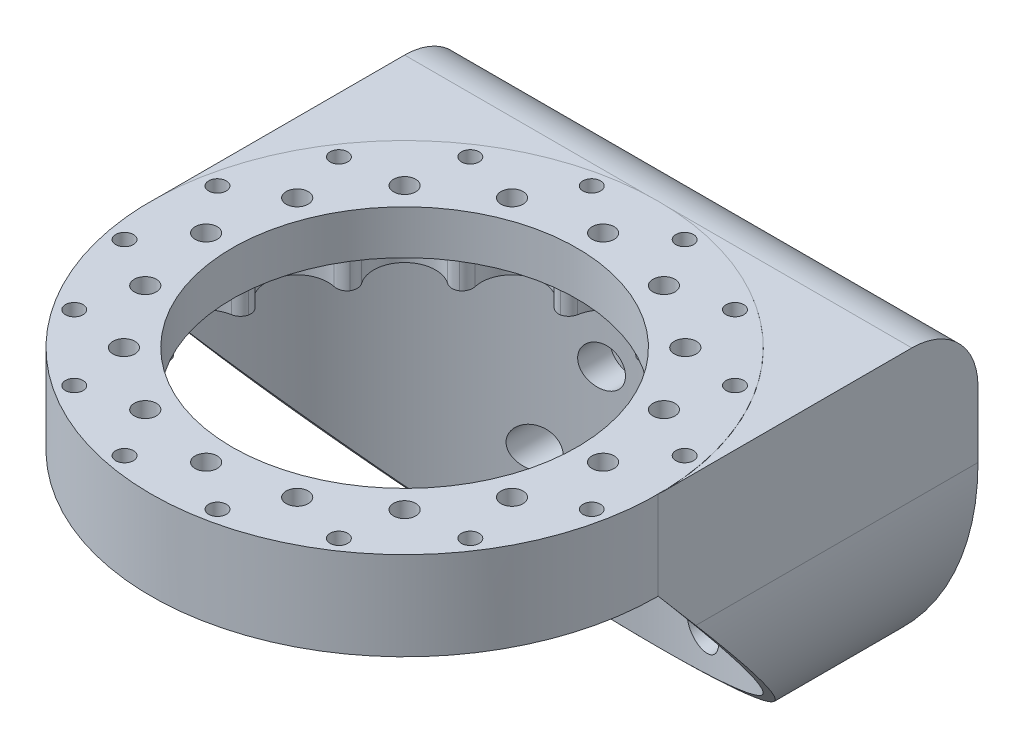
SolidWorks part; units mm, degrees
ref_plane "Front Plane" through (0, 0, 0) normal (0, 0, 1) x (1, 0, 0)
ref_plane "Top Plane" through (0, 0, 0) normal (0, 1, 0) x (1, 0, 0)
ref_plane "Right Plane" through (0, 0, 0) normal (1, 0, 0) x (0, 0, -1)
sketch "Sketch1" plane through (0, 0, 0) normal (0, 1, 0) x (1, 0, 0)
  line L0 (-10.5349, 52.9624) -> (0, 0) construction
  line L1 (0, 0) -> (24.6214, 0) construction
  circle A12 centre (0, 0) radius 39.1
  circle A13 centre (0, 0) radius 57.5
  circle A14 centre (0, 0) radius 54 construction
  circle A15 centre (-10.5349, 52.9624) radius 2
  circle A16 centre (10.5349, 52.9624) radius 2
  circle A17 centre (30.0008, 44.8994) radius 2
  circle A18 centre (44.8994, 30.0008) radius 2
  circle A19 centre (52.9624, 10.5349) radius 2
  circle A20 centre (52.9624, -10.5349) radius 2
  circle A21 centre (44.8994, -30.0008) radius 2
  circle A22 centre (30.0008, -44.8994) radius 2
  circle A23 centre (10.5349, -52.9624) radius 2
  circle A24 centre (-10.5349, -52.9624) radius 2
  circle A25 centre (-30.0008, -44.8994) radius 2
  circle A26 centre (-44.8994, -30.0008) radius 2
  circle A47 centre (-52.9624, -10.5349) radius 2
  circle A48 centre (-52.9624, 10.5349) radius 2
  circle A49 centre (-44.8994, 30.0008) radius 2
  circle A50 centre (-30.0008, 44.8994) radius 2
  point P21 (0, 0)
  point P28 (0, 0)
  point P56 (0, 0)
  point P60 (0, 0)
  dimension "D1" = 101.25
  dimension "D4" = 115
  dimension "D5" = 78.2
  dimension "D6" = 108
  dimension "D7" = 4
  dimension "D8" = 16
extrude "Boss-Extrude1" add sketch "Sketch1" along normal blind 10
sketch "Sketch2" plane through (0, 10, 0) normal (0, 1, 0) x (1, 0, 0)
  circle A0 centre (0, 0) radius 45 construction
  circle A1 centre (0, 45) radius 2.5
  circle A2 centre (17.2208, 41.5746) radius 2.5
  circle A3 centre (31.8198, 31.8198) radius 2.5
  circle A4 centre (41.5746, 17.2208) radius 2.5
  circle A5 centre (45, 0) radius 2.5
  circle A6 centre (41.5746, -17.2208) radius 2.5
  circle A7 centre (31.8198, -31.8198) radius 2.5
  circle A8 centre (17.2208, -41.5746) radius 2.5
  circle A9 centre (0, -45) radius 2.5
  circle A10 centre (-17.2208, -41.5746) radius 2.5
  circle A11 centre (-31.8198, -31.8198) radius 2.5
  circle A12 centre (-41.5746, -17.2208) radius 2.5
  circle A13 centre (-45, 0) radius 2.5
  circle A14 centre (-41.5746, 17.2208) radius 2.5
  circle A15 centre (-31.8198, 31.8198) radius 2.5
  circle A16 centre (-17.2208, 41.5746) radius 2.5
  point P27 (0, 0)
  dimension "D1" = 90
  dimension "D2" = 5
  dimension "D3" = 16
extrude "Cut-Extrude1" cut sketch "Sketch2" against normal blind 10
sketch "Sketch4" plane through (0, 0, 0) normal (0, 1, 0) x (1, 0, 0)
  circle A0 centre (0, 0) radius 45 construction
  circle A1 centre (0, 45) radius 5
  circle A2 centre (0, 45) radius 2.5
  circle A3 centre (17.2208, 41.5746) radius 2.5
  circle A4 centre (31.8198, 31.8198) radius 2.5
  circle A5 centre (41.5746, 17.2208) radius 2.5
  circle A6 centre (45, 0) radius 2.5
  circle A7 centre (41.5746, -17.2208) radius 2.5
  circle A8 centre (31.8198, -31.8198) radius 2.5
  circle A9 centre (17.2208, -41.5746) radius 2.5
  circle A10 centre (0, -45) radius 2.5
  circle A11 centre (-17.2208, -41.5746) radius 2.5
  circle A12 centre (-31.8198, -31.8198) radius 2.5
  circle A13 centre (17.2208, 41.5746) radius 5
  circle A14 centre (31.8198, 31.8198) radius 5
  circle A15 centre (41.5746, 17.2208) radius 5
  circle A16 centre (45, 0) radius 5
  circle A17 centre (41.5746, -17.2208) radius 5
  circle A18 centre (31.8198, -31.8198) radius 5
  circle A19 centre (17.2208, -41.5746) radius 5
  circle A20 centre (0, -45) radius 5
  circle A21 centre (-17.2208, -41.5746) radius 5
  circle A22 centre (-31.8198, -31.8198) radius 5
  circle A23 centre (-41.5746, -17.2208) radius 5
  circle A24 centre (-45, 0) radius 5
  circle A25 centre (-41.5746, 17.2208) radius 5
  circle A26 centre (-31.8198, 31.8198) radius 5
  circle A27 centre (-17.2208, 41.5746) radius 5
  circle A28 centre (-41.5746, -17.2208) radius 2.5
  circle A29 centre (-45, 0) radius 2.5
  circle A30 centre (-41.5746, 17.2208) radius 2.5
  circle A31 centre (-31.8198, 31.8198) radius 2.5
  circle A32 centre (-17.2208, 41.5746) radius 2.5
  point P29 (0, 0)
  point P50 (0, 0)
  dimension "D1" = 10
  dimension "D2" = 16
  dimension "D3" = 16
extrude "Boss-Extrude3" add sketch "Sketch4" against normal blind 0.4
sketch "Sketch5" plane through (0, 0, 0) normal (0, -1, 0) x (1, 0, 0)
  circle A0 centre (0, 0) radius 57.5
  circle A1 centre (0, 0) radius 45
  circle A2 centre (0, 45) radius 7
  circle A3 centre (17.2208, 41.5746) radius 7
  circle A4 centre (31.8198, 31.8198) radius 7
  circle A5 centre (41.5746, 17.2208) radius 7
  circle A6 centre (45, 0) radius 7
  circle A7 centre (41.5746, -17.2208) radius 7
  circle A8 centre (31.8198, -31.8198) radius 7
  circle A9 centre (17.2208, -41.5746) radius 7
  circle A10 centre (0, -45) radius 7
  circle A11 centre (-17.2208, -41.5746) radius 7
  circle A12 centre (-31.8198, -31.8198) radius 7
  circle A13 centre (-41.5746, -17.2208) radius 7
  circle A14 centre (-45, 0) radius 7
  circle A15 centre (-41.5746, 17.2208) radius 7
  circle A16 centre (-31.8198, 31.8198) radius 7
  circle A17 centre (-17.2208, 41.5746) radius 7
  circle A18 centre (0, 0) radius 54 construction
  circle A19 centre (-10.5349, 52.9624) radius 2
  circle A20 centre (10.5349, 52.9624) radius 2
  circle A21 centre (30.0008, 44.8994) radius 2
  circle A22 centre (44.8994, 30.0008) radius 2
  circle A23 centre (52.9624, 10.5349) radius 2
  circle A24 centre (52.9624, -10.5349) radius 2
  circle A25 centre (44.8994, -30.0008) radius 2
  circle A26 centre (30.0008, -44.8994) radius 2
  circle A27 centre (10.5349, -52.9624) radius 2
  circle A28 centre (-10.5349, -52.9624) radius 2
  circle A29 centre (-30.0008, -44.8994) radius 2
  circle A30 centre (-44.8994, -30.0008) radius 2
  circle A31 centre (-52.9624, -10.5349) radius 2
  circle A32 centre (-52.9624, 10.5349) radius 2
  circle A33 centre (-44.8994, 30.0008) radius 2
  circle A34 centre (-30.0008, 44.8994) radius 2
  point P39 (0, 0)
  point P75 (0, 0)
  circle M34 centre (0, 0) radius 57.5
  circle M35 centre (-52.9624, 10.5349) radius 2
  circle M37 centre (-52.9624, -10.5349) radius 2
  circle M39 centre (-30.0008, -44.8994) radius 2
  circle M41 centre (10.5349, -52.9624) radius 2
  circle M43 centre (44.8994, -30.0008) radius 2
  circle M45 centre (52.9624, 10.5349) radius 2
  circle M47 centre (30.0008, 44.8994) radius 2
  circle M49 centre (-10.5349, 52.9624) radius 2
  dimension "D1" = 14
  dimension "D2" = 16
  dimension "D3" = 16
extrude "Boss-Extrude4" add sketch "Sketch5" along normal blind 10.06 contours A17 A1 A2 A3 A4 A5 A6 A7 A8 A9 A10 A11 A12 A13 A14 A15 A16 M34 M35 M37 M39 M41 M43 M45 M47 M49 region at (-55.8737, 0, 0)
fillet "Fillet2" radius 2.5 32 edges at (-23.46, -5.03, -38.4009) (-26.5001, -5.03, -36.3696) (-6.9788, -5.03, -44.4556) (-10.5648, -5.03, -43.7422) (10.5648, -5.03, -43.7422) (6.9788, -5.03, -44.4556) (26.5001, -5.03, -36.3696) (23.46, -5.03, -38.4009) (38.4009, -5.03, -23.46) (36.3696, -5.03, -26.5001) (44.4556, -5.03, -6.9788) (43.7422, -5.03, -10.5648) (43.7422, -5.03, 10.5648) (44.4556, -5.03, 6.9788) (-38.4009, -5.03, -23.46) (-36.3696, -5.03, -26.5001) (-44.4556, -5.03, -6.9788) (-43.7422, -5.03, -10.5648) (-43.7422, -5.03, 10.5648) (-44.4556, -5.03, 6.9788) (-36.3696, -5.03, 26.5001) (-38.4009, -5.03, 23.46) (-23.46, -5.03, 38.4009) (-26.5001, -5.03, 36.3696) (-10.5648, -5.03, 43.7422) (-6.9788, -5.03, 44.4556) (6.9788, -5.03, 44.4556) (10.5648, -5.03, 43.7422) (23.46, -5.03, 38.4009) (26.5001, -5.03, 36.3696) (38.4009, -5.03, 23.46) (36.3696, -5.03, 26.5001)
sketch "Sketch6" plane through (0, -10.06, 0) normal (0, -1, 0) x (1, 0, 0)
  line L0 (-57.5, 0) -> (57.5, 0) construction
  line L1 (57.5, 0) -> (57.5, -57.5)
  line L2 (57.5, -57.5) -> (-57.5, -57.5)
  line L3 (-57.5, -57.5) -> (-57.5, 0)
  circle A0 centre (0, 0) radius 57.5 construction
  arc A1 (-57.5, 0) -> (57.5, 0) centre (0, 0) ccw
extrude "Boss-Extrude7" add sketch "Sketch6" against normal blind 20 contours A1 L2 L1 | A1 L3 L2 region at (-44.6563, -10.06, -44.6563) region at (44.6563, -10.06, -44.6563)
sketch "Sketch7" plane through (-57.5, 0, 0) normal (-1, 0, 0) x (0, 0, 1)
  line L0 (-57.5, 9.94) -> (-57.5, -77.56)
  line L1 (-57.5, -77.56) -> (-72.5, -77.56)
  line L2 (-72.5, -77.56) -> (-72.5, 9.94)
  line L3 (-72.5, 9.94) -> (-57.5, 9.94)
  line L4 (-57.5, -77.56) -> (0, -10.06)
  line L5 (0, -10.06) -> (-57.5, -10.06)
  line M5 (-57.5, -10.06) -> (0, -10.06)
  line M8 (-57.5, 9.94) -> (-57.5, -10.06)
  dimension "D1" = 15
  dimension "D2" = 87.5
  dimension "D3" = 67.5
extrude "Boss-Extrude8" add sketch "Sketch7" against normal blind 115 contours L3 L2 L1 L0 M8 | L0 L4 M5 region at (-57.5, -33.81, -65) region at (-57.5, -32.56, -38.3333)
sketch "Sketch8" plane through (0, -77.56, 0) normal (0, -1, 0) x (1, 0, 0)
  circle A0 centre (0, 0) radius 57.5
extrude "Cut-Extrude2" cut sketch "Sketch8" against normal blind 67.5
sketch "Sketch9" plane through (0, 0, -72.5) normal (0, 0, -1) x (-1, 0, 0)
  line L0 (0, 19.2611) -> (0, -105.8991) construction
  line L1 (-57.5, -77.56) -> (57.5, -77.56) construction
  circle A0 centre (0, -47.56) radius 30 construction
  circle A1 centre (0, -47.56) radius 23 construction
  circle A2 centre (23, -47.56) radius 2.25
  circle A3 centre (11.5, -67.4786) radius 2.25
  circle A4 centre (-11.5, -67.4786) radius 2.25
  circle A5 centre (-23, -47.56) radius 2.25
  circle A6 centre (-11.5, -27.6414) radius 2.25
  circle A7 centre (11.5, -27.6414) radius 2.25
  point P22 (0, -47.56)
  dimension "D1" = 60
  dimension "D2" = 46
  dimension "D3" = 4.5
  dimension "D4" = 6
extrude "Cut-Extrude3" cut sketch "Sketch9" against normal blind 67.5
sketch "Sketch10" plane through (0, 0, 0) normal (0, 0, 1) x (1, 0, 0)
  line L0 (57.5, -77.56) -> (0, -77.56) construction
  circle A0 centre (0, -47.56) radius 30 construction
  circle A1 centre (0, -47.56) radius 23 construction
  circle A2 centre (23, -47.56) radius 4.5
  circle A3 centre (11.5, -67.4786) radius 4.5
  circle A4 centre (-11.5, -67.4786) radius 4.5
  circle A5 centre (-23, -47.56) radius 4.5
  circle A6 centre (-11.5, -27.6414) radius 4.5
  circle A7 centre (11.5, -27.6414) radius 4.5
  point P19 (0, -47.56)
  dimension "D1" = 60
  dimension "D2" = 46
  dimension "D3" = 9
  dimension "D4" = 6
extrude "Cut-Extrude4" cut sketch "Sketch10" against normal blind 62.5
sketch "Sketch11" plane through (0, 0, -72.5) normal (0, 0, -1) x (-1, 0, 0)
  line L0 (0, 13.9005) -> (0, -82.4311) construction
  line L1 (-57.5, -77.56) -> (57.5, -77.56) construction
  line L2 (-57.5, -20.06) -> (-57.5, -77.56)
  line L3 (-57.5, -77.56) -> (57.5, -77.56)
  line L4 (57.5, -77.56) -> (57.5, -20.06)
  circle A0 centre (0, -20.06) radius 57.5
  line M8 (57.5, -77.56) -> (57.5, 9.94)
  line M10 (-57.5, 9.94) -> (-57.5, -77.56)
  line M11 (-57.5, -77.56) -> (57.5, -77.56)
  dimension "D1" = 115
extrude "Cut-Extrude5" cut sketch "Sketch11" against normal blind 133 contours A0 M10 M11 | A0 L3 M8 region at (44.6563, -64.7163, -72.5) region at (-44.6563, -64.7163, -72.5)
fillet "Fillet4" radius 15 1 edges at (0, 9.94, -72.5)
